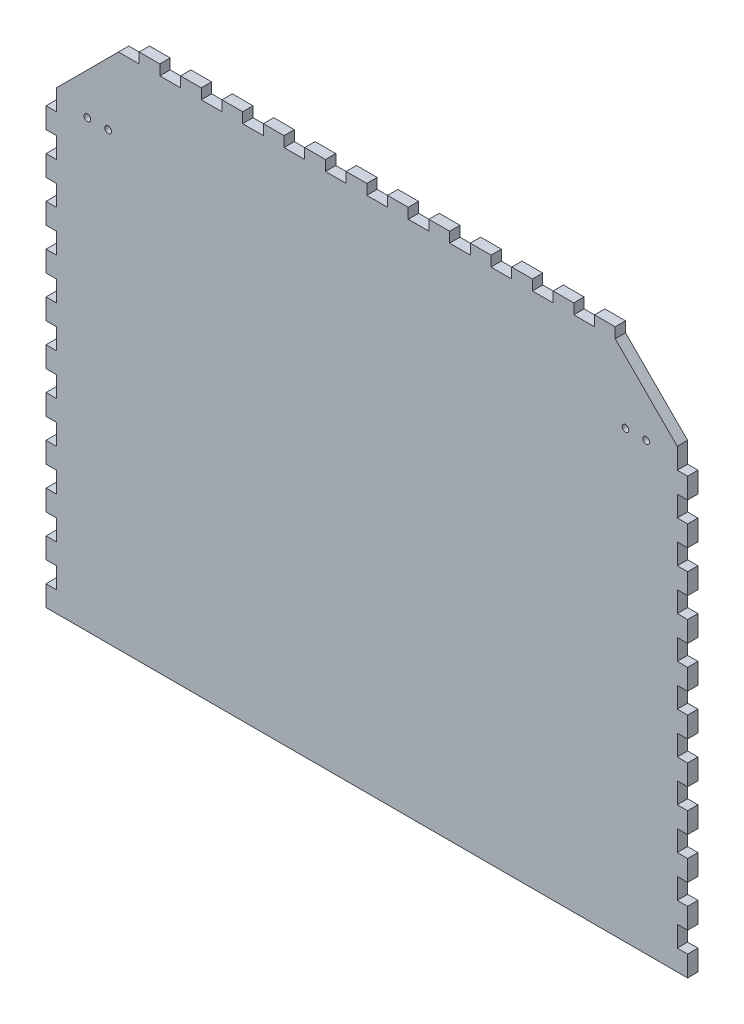
SolidWorks part; units mm, degrees
material "Buche"
ref_plane "Ebene vorne" through (0, 0, 0) normal (0, 0, 1) x (1, 0, 0)
ref_plane "Ebene oben" through (0, 0, 0) normal (0, 1, 0) x (1, 0, 0)
ref_plane "Ebene rechts" through (0, 0, 0) normal (1, 0, 0) x (0, 0, -1)
sketch "Skizze1" plane through (0, 0, 0) normal (0, 0, 1) x (1, 0, 0)
  line L0 (5, 10) -> (5, 20)
  line L1 (5, 0) -> (305, 0)
  line L2 (305, 10) -> (305, 20)
  line L3 (55, 250) -> (65, 250)
  line L4 (5, 220) -> (35, 250)
  line L5 (305, 220) -> (275, 250)
  line L6 (35, 250) -> (45, 250)
  line L7 (45, 250) -> (45, 255)
  line L8 (45, 255) -> (55, 255)
  line L9 (55, 255) -> (55, 250)
  line L10 (65, 250) -> (65, 255)
  line L11 (65, 255) -> (75, 255)
  line L12 (75, 255) -> (75, 250)
  line L13 (305, 0) -> (310, 0)
  line L14 (310, 0) -> (310, 10)
  line L15 (310, 10) -> (305, 10)
  line L16 (305, 30) -> (305, 40)
  line L17 (305, 20) -> (310, 20)
  line L18 (310, 20) -> (310, 30)
  line L19 (310, 30) -> (305, 30)
  line L20 (305, 50) -> (305, 60)
  line L21 (305, 40) -> (310, 40)
  line L22 (310, 40) -> (310, 50)
  line L23 (310, 50) -> (305, 50)
  line L24 (305, 70) -> (305, 80)
  line L25 (305, 60) -> (310, 60)
  line L26 (310, 60) -> (310, 70)
  line L27 (310, 70) -> (305, 70)
  line L28 (305, 90) -> (305, 100)
  line L29 (305, 80) -> (310, 80)
  line L30 (310, 80) -> (310, 90)
  line L31 (310, 90) -> (305, 90)
  line L32 (305, 110) -> (305, 120)
  line L33 (305, 100) -> (310, 100)
  line L34 (310, 100) -> (310, 110)
  line L35 (310, 110) -> (305, 110)
  line L36 (305, 130) -> (305, 140)
  line L37 (305, 120) -> (310, 120)
  line L38 (310, 120) -> (310, 130)
  line L39 (310, 130) -> (305, 130)
  line L40 (305, 150) -> (305, 160)
  line L41 (305, 140) -> (310, 140)
  line L42 (310, 140) -> (310, 150)
  line L43 (310, 150) -> (305, 150)
  line L44 (305, 170) -> (305, 180)
  line L45 (305, 160) -> (310, 160)
  line L46 (310, 160) -> (310, 170)
  line L47 (310, 170) -> (305, 170)
  line L48 (305, 190) -> (305, 200)
  line L49 (305, 180) -> (310, 180)
  line L50 (310, 180) -> (310, 190)
  line L51 (310, 190) -> (305, 190)
  line L52 (305, 210) -> (305, 220)
  line L53 (305, 200) -> (310, 200)
  line L54 (310, 200) -> (310, 210)
  line L55 (310, 210) -> (305, 210)
  line L56 (5, 0) -> (0, 0)
  line L57 (0, 0) -> (0, 10)
  line L58 (0, 10) -> (5, 10)
  line L59 (5, 30) -> (5, 40)
  line L60 (0, 20) -> (0, 30)
  line L61 (0, 30) -> (5, 30)
  line L62 (5, 50) -> (5, 60)
  line L63 (0, 40) -> (0, 50)
  line L64 (0, 50) -> (5, 50)
  line L65 (5, 70) -> (5, 80)
  line L66 (0, 60) -> (0, 70)
  line L67 (0, 70) -> (5, 70)
  line L68 (5, 90) -> (5, 100)
  line L69 (0, 80) -> (0, 90)
  line L70 (0, 90) -> (5, 90)
  line L71 (5, 110) -> (5, 120)
  line L72 (0, 100) -> (0, 110)
  line L73 (0, 110) -> (5, 110)
  line L74 (5, 130) -> (5, 140)
  line L75 (0, 120) -> (0, 130)
  line L76 (0, 130) -> (5, 130)
  line L77 (5, 150) -> (5, 160)
  line L78 (0, 140) -> (0, 150)
  line L79 (0, 150) -> (5, 150)
  line L80 (5, 170) -> (5, 180)
  line L81 (0, 160) -> (0, 170)
  line L82 (0, 170) -> (5, 170)
  line L83 (5, 190) -> (5, 200)
  line L84 (0, 180) -> (0, 190)
  line L85 (0, 190) -> (5, 190)
  line L86 (5, 210) -> (5, 220)
  line L87 (0, 200) -> (0, 210)
  line L88 (0, 210) -> (5, 210)
  line L89 (0, 20) -> (5, 20)
  line L90 (0, 40) -> (5, 40)
  line L91 (0, 60) -> (5, 60)
  line L92 (0, 80) -> (5, 80)
  line L93 (0, 100) -> (5, 100)
  line L94 (0, 120) -> (5, 120)
  line L95 (0, 140) -> (5, 140)
  line L96 (0, 160) -> (5, 160)
  line L97 (0, 180) -> (5, 180)
  line L98 (0, 200) -> (5, 200)
  line L99 (75, 250) -> (85, 250)
  line L100 (85, 250) -> (85, 255)
  line L101 (85, 255) -> (95, 255)
  line L102 (95, 255) -> (95, 250)
  line L103 (95, 250) -> (105, 250)
  line L104 (105, 250) -> (105, 255)
  line L105 (105, 255) -> (115, 255)
  line L106 (115, 255) -> (115, 250)
  line L107 (115, 250) -> (125, 250)
  line L108 (125, 250) -> (125, 255)
  line L109 (125, 255) -> (135, 255)
  line L110 (135, 255) -> (135, 250)
  line L111 (135, 250) -> (145, 250)
  line L112 (145, 250) -> (145, 255)
  line L113 (145, 255) -> (155, 255)
  line L114 (155, 255) -> (155, 250)
  line L115 (155, 250) -> (165, 250)
  line L116 (165, 250) -> (165, 255)
  line L117 (165, 255) -> (175, 255)
  line L118 (175, 255) -> (175, 250)
  line L119 (175, 250) -> (185, 250)
  line L120 (185, 250) -> (185, 255)
  line L121 (185, 255) -> (195, 255)
  line L122 (195, 255) -> (195, 250)
  line L123 (195, 250) -> (205, 250)
  line L124 (205, 250) -> (205, 255)
  line L125 (205, 255) -> (215, 255)
  line L126 (215, 255) -> (215, 250)
  line L127 (215, 250) -> (225, 250)
  line L128 (225, 250) -> (225, 255)
  line L129 (225, 255) -> (235, 255)
  line L130 (235, 255) -> (235, 250)
  line L131 (235, 250) -> (245, 250)
  line L132 (245, 250) -> (245, 255)
  line L133 (245, 255) -> (255, 255)
  line L134 (255, 255) -> (255, 250)
  line L135 (255, 250) -> (265, 250)
  line L136 (265, 250) -> (265, 255)
  line L137 (265, 255) -> (275, 255)
  line L138 (275, 255) -> (275, 250)
  circle A0 centre (20, 215) radius 1.6
  circle A1 centre (30, 215) radius 1.6
  circle A2 centre (290, 215) radius 1.6
  circle A3 centre (280, 215) radius 1.6
  dimension "D1" = 12
extrude "Aufsatz-Linear austragen1" add sketch "Skizze1" along normal blind 5
